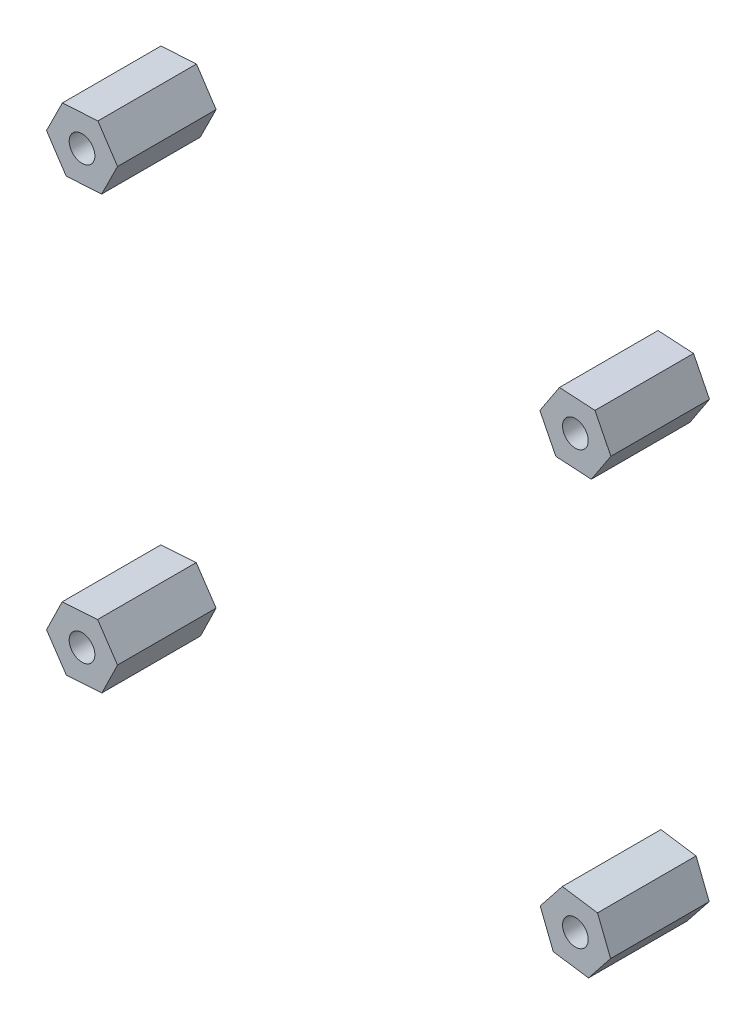
SolidWorks part; units mm, degrees
ref_plane "Front Plane" through (0, 0, 0) normal (0, 0, 1) x (1, 0, 0)
ref_plane "Top Plane" through (0, 0, 0) normal (0, 1, 0) x (1, 0, 0)
ref_plane "Right Plane" through (0, 0, 0) normal (1, 0, 0) x (0, 0, -1)
sketch "Sketch1" plane through (0, 0, 0) normal (0, 0, 1) x (1, 0, 0)
  line L1 (-204.7734, 103.58) -> (-203.2279, 106.6802)
  line L2 (-203.2279, 106.6802) -> (-205.14, 109.5687)
  line L3 (-205.14, 109.5687) -> (-208.5977, 109.357)
  line L4 (-208.5977, 109.357) -> (-210.1432, 106.2568)
  line L5 (-210.1432, 106.2568) -> (-208.231, 103.3683)
  line L6 (-208.231, 103.3683) -> (-204.7734, 103.58)
  line L7 (-157.0934, 103.3716) -> (-155.1875, 106.2642)
  line L8 (-155.1875, 106.2642) -> (-156.7396, 109.3611)
  line L9 (-156.7396, 109.3611) -> (-160.1977, 109.5654)
  line L10 (-160.1977, 109.5654) -> (-162.1036, 106.6728)
  line L11 (-162.1036, 106.6728) -> (-160.5515, 103.5759)
  line L12 (-160.5515, 103.5759) -> (-157.0934, 103.3716)
  line L13 (-204.7484, 61.5267) -> (-203.2299, 64.6402)
  line L14 (-203.2299, 64.6402) -> (-205.167, 67.512)
  line L15 (-205.167, 67.512) -> (-208.6227, 67.2703)
  line L16 (-208.6227, 67.2703) -> (-210.1412, 64.1568)
  line L17 (-210.1412, 64.1568) -> (-208.204, 61.285)
  line L18 (-208.204, 61.285) -> (-204.7484, 61.5267)
  line L19 (-157.3725, 61.1768) -> (-155.2189, 63.8901)
  line L20 (-155.2189, 63.8901) -> (-156.492, 67.1118)
  line L21 (-156.492, 67.1118) -> (-159.9185, 67.6202)
  line L22 (-159.9185, 67.6202) -> (-162.0721, 64.9069)
  line L23 (-162.0721, 64.9069) -> (-160.7991, 61.6852)
  line L24 (-160.7991, 61.6852) -> (-157.3725, 61.1768)
  circle A0 centre (-206.6855, 106.4685) radius 3 construction
  circle A1 centre (-158.6455, 106.4685) radius 3 construction
  circle A2 centre (-206.6855, 64.3985) radius 3 construction
  circle A3 centre (-158.6455, 64.3985) radius 3 construction
  circle A4 centre (-206.6855, 106.4685) radius 1.25
  circle A5 centre (-158.6455, 106.4685) radius 1.25
  circle A6 centre (-206.6855, 64.3985) radius 1.25
  circle A7 centre (-158.6455, 64.3985) radius 1.25
  dimension "D5" = 2.5
  dimension "D1" = 6
  dimension "D2" = 6
  dimension "D3" = 6
  dimension "D4" = 6
extrude "Boss-Extrude1" add sketch "Sketch1" along normal blind 9.6
ref_axis "Axis1" through (-206.6855, 106.4685, 9.6) along (0, 0, -1)
ref_axis "Axis2" through (-158.6455, 106.4685, 9.6) along (0, 0, -1)
equation "\"D2@Sketch1\"=\"D1@Sketch1\""
equation "\"D3@Sketch1\"=\"D1@Sketch1\""
equation "\"D4@Sketch1\"=\"D1@Sketch1\""
